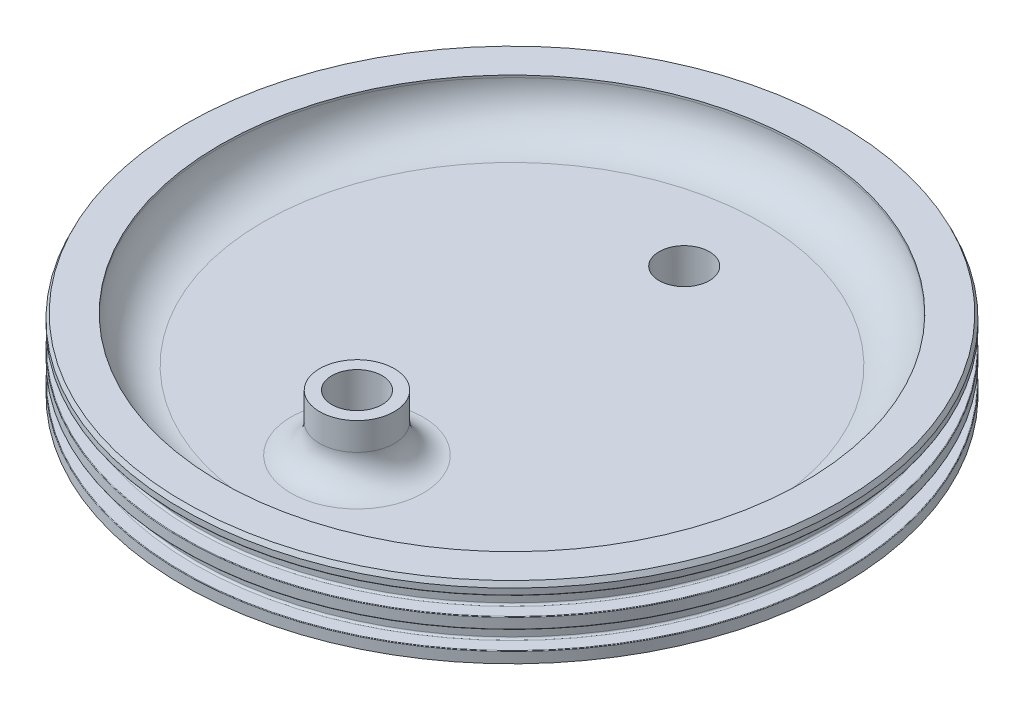
SolidWorks part; units mm, degrees
material "6061-T6 (SS)"
ref_plane "Front Plane" through (0, 0, 0) normal (0, 0, 1) x (1, 0, 0)
ref_plane "Top Plane" through (0, 0, 0) normal (0, 1, 0) x (1, 0, 0)
ref_plane "Right Plane" through (0, 0, 0) normal (1, 0, 0) x (0, 0, -1)
sketch "Sketch1" plane through (0, 0, 0) normal (0, 0, 1) x (1, 0, 0)
  line L0 (0, 48.1922) -> (0, -25.6743) construction
  line L1 (0, 0) -> (72.898, 0)
  line L2 (72.898, 0) -> (72.898, 2.4638)
  line L3 (72.898, 2.4638) -> (69.6468, 2.4638)
  line L4 (69.6468, 2.4638) -> (69.6468, 6.5278)
  line L5 (69.6468, 6.5278) -> (72.898, 6.5278)
  line L6 (72.898, 6.5278) -> (72.898, 8.9916)
  line L7 (72.898, 8.9916) -> (69.6468, 8.9916)
  line L8 (64.5668, 15.5956) -> (64.5668, 5.588)
  line L9 (64.5668, 5.588) -> (0, 5.588)
  line L10 (0, 5.588) -> (0, 0)
  line L11 (69.6468, 8.9916) -> (69.6468, 13.0556)
  line L12 (69.6468, 13.0556) -> (72.898, 13.0556)
  line L13 (72.898, 13.0556) -> (72.898, 15.5956)
  line L14 (72.898, 15.5956) -> (64.5668, 15.5956)
  dimension "D1" = 145.796
  dimension "D2" = 4.064
  dimension "D5" = 5.588
  dimension "D7" = 4.064
  dimension "D4" = 2.4638
  dimension "D8" = 2.54
  dimension "D3" = 69.6468
  dimension "D6" = 5.08
revolve "Revolve1" add sketch "Sketch1" angle 360 about L0
sketch "Sketch6" plane through (0, 0, 0) normal (0, -1, 0) x (1, 0, 0)
  circle A0 centre (0, 0) radius 66.04
  dimension "D1" = 132.08
extrude "Boss-Extrude1" add sketch "Sketch6" along normal blind 2.54
hole_wizard "Pipe Tap Drill for 1/4 Tap - GN2" positions "Sketch2" profile "Sketch3" hole size "1/4" standard "ANSI Inch" end condition through all
sketch "Sketch2" plane through (0, 5.588, 0) normal (0, 1, 0) x (1, 0, 0)
  point P4 (0, -34.29)
  dimension "D1" = 34.29
sketch "Sketch3" plane through (0, 5.588, 34.29) normal (1, 0, 0) x (0, 0, 1)
  line L0 (0, 0) -> (0, 8.128)
  line L1 (0, 8.128) -> (5.5626, 8.128)
  line L2 (5.5626, 8.128) -> (5.5626, 0)
  line L5 (5.5626, 0) -> (0, 0)
  line L11 (0, -6.35) -> (0, 107.95) construction
  dimension "Thru Hole Dia." = 11.1252
  dimension "Thru Hole Depth" = 8.128
fillet "CNC ID Fillet" radius 0.4064 5 edges at (-69.6468, 6.5278, 0) (-69.6468, 2.4638, 0) (-69.6468, 13.0556, 0) (-69.6468, 8.9916, 0) (66.04, 0, 0)
fillet "CNC OD Fillet" radius 0.127 5 edges at (-72.898, 6.5278, 0) (-72.898, 2.4638, 0) (66.04, -2.54, 0) (-72.898, 13.0556, 0) (-72.898, 8.9916, 0)
chamfer "CNC Chamfers" distance 0.508 angle 65 1 edges at (-72.898, 15.5956, 0) first distance on face at (-64.5668, 15.5956, 0)
hole_wizard "Pipe Tap Drill for 1/4 Tap - Relief Valve" positions "Sketch13" profile "Sketch14" hole size "1/4" standard "ANSI Inch" end condition through all
sketch "Sketch13" plane through (0, -2.54, 0) normal (0, -1, 0) x (-1, 0, 0)
  point P4 (0, 38.1)
  dimension "D1" = 38.1
sketch "Sketch14" plane through (0, -2.54, -38.1) normal (1, 0, 0) x (0, 0, -1)
  line L0 (0, 0) -> (0, 18.1356)
  line L1 (0, 18.1356) -> (5.5626, 18.1356)
  line L2 (5.5626, 18.1356) -> (5.5626, 0)
  line L5 (5.5626, 0) -> (0, 0)
  line L11 (0, -6.35) -> (0, 107.95) construction
  dimension "Thru Hole Dia." = 11.1252
  dimension "Thru Hole Depth" = 18.1356
sketch "Sketch15" plane through (0, -2.54, 0) normal (0, -1, 0) x (1, 0, 0)
  circle A0 centre (0, 34.29) radius 8.255
  circle A1 centre (0, 34.29) radius 5.5626 construction
  circle A2 centre (0, 34.29) radius 5.5626
  dimension "D1" = 16.51
extrude "Boss-Extrude2" add sketch "Sketch15" against normal blind 12.446 from surface starting at face at (5.5626, 5.588, -38.1)
fillet "Fillet2" radius 6.35 1 edges at (8.255, 5.588, 34.29)
fillet "Fillet3" radius 9.525 1 edges at (-64.5668, 5.588, 0)
sketch "Sketch16" plane through (0, -2.54, 0) normal (0, -1, 0) x (1, 0, 0)
  line L0 (0, 34.29) -> (0, -38.1) construction
  line L1 (25.4, 26.67) -> (-25.4, 26.67) construction
  line L2 (-9.4223, -1.905) -> (9.4223, -1.905) construction
  line L3 (25.4, -30.48) -> (-25.4, -30.48) construction
  text T0 "GN2"
  text T1 "VENT\r\n"
  point P7 (0, 26.67)
  point P14 (0, -1.905)
  dimension "D1" = 50.8
  dimension "D2" = 7.62
equation "\"D3@Sketch1\"=5.484/2"
